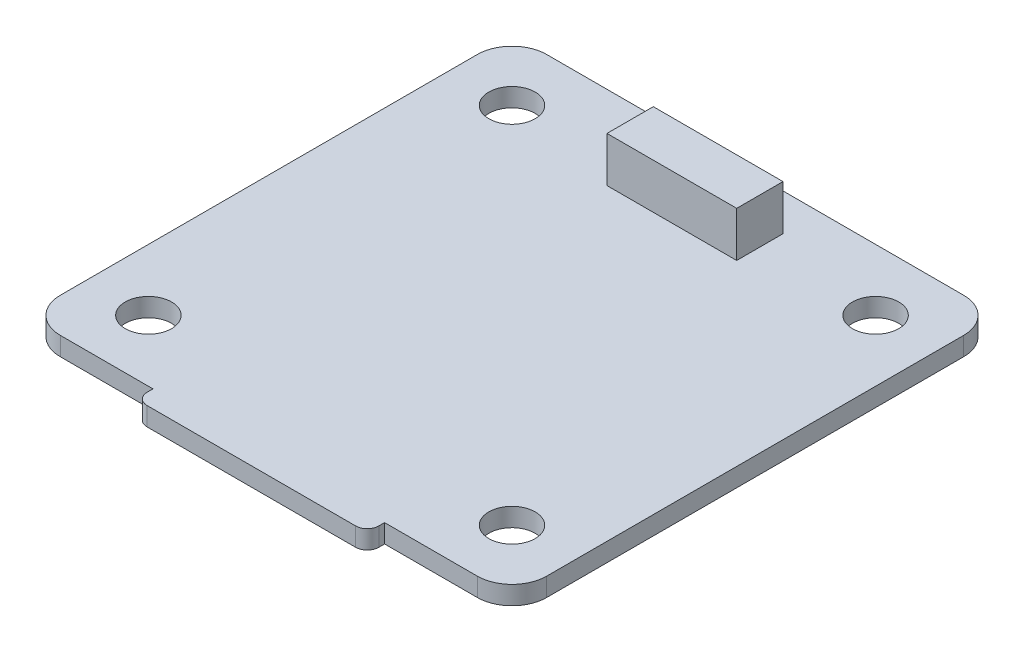
SolidWorks part; units mm, degrees
ref_plane "Płaszczyzna przednia" through (0, 0, 0) normal (0, 0, 1) x (1, 0, 0)
ref_plane "Płaszczyzna górna" through (0, 0, 0) normal (0, 1, 0) x (1, 0, 0)
ref_plane "Płaszczyzna prawa" through (0, 0, 0) normal (1, 0, 0) x (0, 0, -1)
sketch "Szkic2" plane through (0, 0, 0) normal (0, 1, 0) x (1, 0, 0)
  line L0 (-10, -21) -> (-10, -21.5)
  line L5 (-18, -21) -> (-10, -21)
  line L6 (-21, -18) -> (-21, 18)
  line L11 (-18, 21) -> (18, 21)
  line L13 (21, -18) -> (21, 18)
  line L14 (-21, -21) -> (21, 21) construction
  line L15 (-21, 21) -> (21, -21) construction
  line L16 (-9, -22.5) -> (9, -22.5)
  line L17 (10, -21.5) -> (10, -21)
  line L18 (0, 0) -> (0, 20.5) construction
  line L19 (0, 0) -> (21.25, 0) construction
  line L20 (10, -21) -> (18, -21)
  arc A0 (-9, -22.5) -> (-10, -21.5) centre (-9, -21.5) cw
  arc A1 (10, -21.5) -> (9, -22.5) centre (9, -21.5) cw
  arc A2 (-18, 21) -> (-21, 18) centre (-18, 18) ccw
  arc A3 (21, 18) -> (18, 21) centre (18, 18) ccw
  arc A4 (18, -21) -> (21, -18) centre (18, -18) ccw
  arc A5 (-21, -18) -> (-18, -21) centre (-18, -18) ccw
  circle A6 centre (15.6967, 15.6967) radius 2
  circle A7 centre (-15.6967, 15.6967) radius 2
  circle A8 centre (15.6967, -15.6967) radius 2
  circle A9 centre (-15.6967, -15.6967) radius 2
  point P0 (0, 0)
  point P37 (0, 0)
  dimension "D5" = 3
  dimension "D6" = 3
  dimension "D3" = 1
  dimension "D4" = 1
  dimension "D7" = 3
  dimension "D8" = 3
  dimension "D9" = 7.5
  dimension "D12" = 4
  dimension "D1" = 11
  dimension "D2" = 11
  dimension "D10" = 42
  dimension "D11" = 42
extrude "Dodanie-wyciągnięcie1" add sketch "Szkic2" along normal blind 1.6 contours L11 A3 L13 A4 L20 L17 A1 L16 A0 L0 L5 A5 L6 A2
extrude "Wytnij-wyciągnięcie1" cut sketch "Szkic2<3>" along normal up to surface (1.6 mm away) contours A9 | A8 | A7 | A6 up to face at (0, 1.6, 9.3153)
sketch "Szkic2<3>" plane through (0, 0, 0) normal (0, 1, 0) x (1, 0, 0) same geometry as "Szkic2"
sketch "Szkic3" plane through (0, 1.6, 0) normal (0, 1, 0) x (1, 0, 0)
  line L0 (0, 0) -> (0, 21) construction
  line L1 (-18, 21) -> (18, 21) construction
  line L3 (-5.6, 13.8) -> (5.6, 13.8)
  line L4 (-5.6, 13.8) -> (-5.6, 17.8)
  line L5 (-5.6, 17.8) -> (5.6, 17.8)
  line L6 (5.6, 13.8) -> (5.6, 17.8)
  line L7 (-5.6, 13.8) -> (5.6, 17.8) construction
  line L8 (-5.6, 17.8) -> (5.6, 13.8) construction
  point P5 (0, 15.8)
  dimension "D1" = 11.2
  dimension "D2" = 4
  dimension "D3" = 3.2
extrude "Dodanie-wyciągnięcie2" add sketch "Szkic3" along normal blind 3.9
